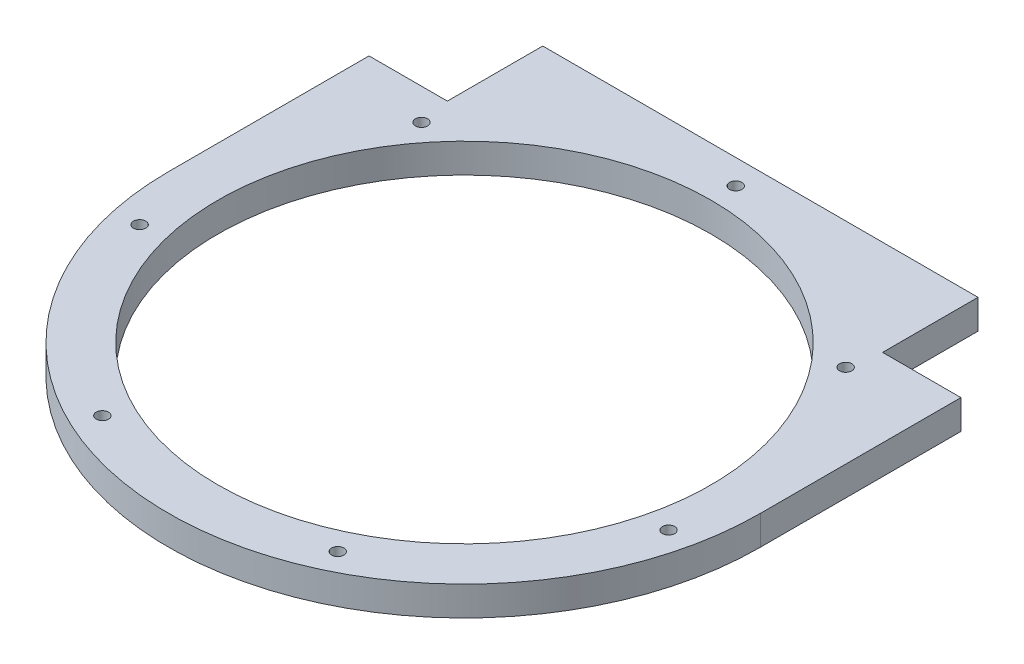
SolidWorks part; units mm, degrees
ref_plane "Front Plane" through (0, 0, 0) normal (0, 0, 1) x (1, 0, 0)
ref_plane "Top Plane" through (0, 0, 0) normal (0, 1, 0) x (1, 0, 0)
ref_plane "Right Plane" through (0, 0, 0) normal (1, 0, 0) x (0, 0, -1)
ref_axis "X Axis" through (-88.99, 0, 0) along (1, 0, 0)
ref_axis "Y Axiz" through (0, 0, 55) along (0, 0, -1)
ref_axis "Z Axis" through (0, 55, 0) along (0, -1, 0)
sketch "Sketch1" plane through (0, 0, 0) normal (0, 1, 0) x (1, 0, 0)
  line L1 (34.4006, 27.4336) -> (31.2733, 24.9396) construction
  line L2 (0, 48) -> (-35.3, 48)
  line L3 (-35.3, 48) -> (-35.3, 32.5255)
  line L4 (-35.3, 32.5255) -> (-48, 32.5255)
  line L5 (-48, 32.5255) -> (-48, 0)
  line L6 (48, 0) -> (-48, 0)
  line L8 (48, 0) -> (48, 32.5255)
  line L9 (48, 32.5255) -> (35.3, 32.5255)
  line L10 (35.3, 32.5255) -> (35.3, 48)
  line L11 (35.3, 48) -> (0, 48)
  circle A0 centre (0, 0) radius 40
  circle A1 centre (0, 0) radius 48
  circle A2 centre (0, 0) radius 44 construction
  circle A3 centre (0, 44) radius 1
  circle A4 centre (34.4006, 27.4336) radius 1
  circle A5 centre (42.8968, -9.7909) radius 1
  circle A6 centre (19.0909, -39.6426) radius 1
  circle A7 centre (-19.0909, -39.6426) radius 1
  circle A8 centre (-42.8968, -9.7909) radius 1
  circle A9 centre (-34.4006, 27.4336) radius 1
  point P24 (0, 0)
  dimension "D1" = 80
  dimension "D2" = 96
  dimension "D3" = 88
  dimension "D4" = 2
  dimension "D6" = 12.7
  dimension "D5" = 7
extrude "Boss-Extrude1" add sketch "Sketch1" along normal blind 4.7625 contours A1 L2 L3 | A1 L4 L5 | L6 A1 A0 A9 A4 A3 | L6 A1 A0 A8 A7 A6 A5 | A1 L8 L9 | A1 L10 L11 region at (-26.7848, 0, -43.5217) region at (26.7848, 0, -43.5217) region at (18.8405, 0, -42.9785) region at (44.2953, 0, -24.625) region at (-44.2953, 0, -24.625) region at (0, 0, 46.9267)
